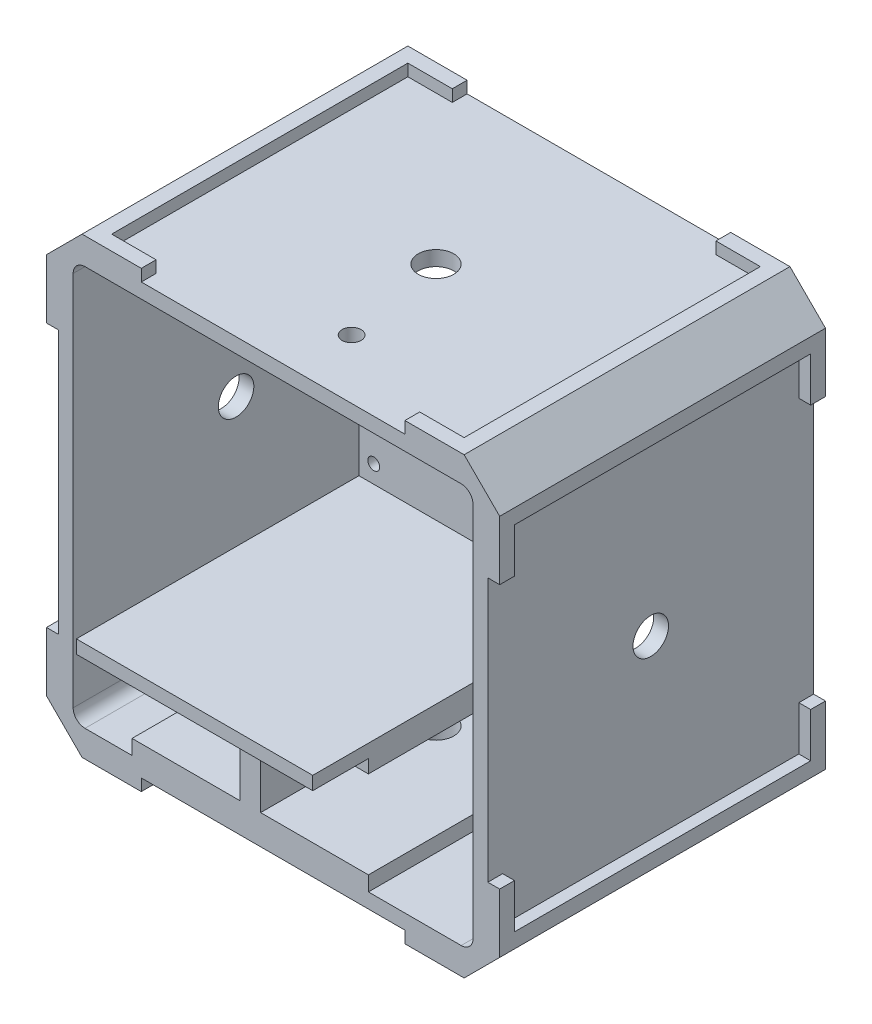
SolidWorks part; units mm, degrees
ref_plane "Front Plane" through (0, 0, 0) normal (0, 0, 1) x (1, 0, 0)
ref_plane "Top Plane" through (0, 0, 0) normal (0, 1, 0) x (1, 0, 0)
ref_plane "Right Plane" through (0, 0, 0) normal (1, 0, 0) x (0, 0, -1)
sketch "Sketch1" plane through (0, 0, 0) normal (0, 0, 1) x (1, 0, 0)
  line L0 (-33.75, -33.75) -> (33.75, -33.75) construction
  line L1 (-31.75, 33.75) -> (31.75, 33.75)
  line L2 (-33.75, 31.75) -> (-33.75, -31.75)
  line L3 (-31.75, -33.75) -> (31.75, -33.75)
  line L4 (33.75, 31.75) -> (33.75, -31.75)
  line L5 (-36.25, 32.25) -> (-36.25, -32.25)
  line L6 (33.75, 33.75) -> (33.75, -33.75) construction
  line L7 (-32.25, -36.25) -> (32.25, -36.25)
  line L8 (36.25, 32.25) -> (36.25, -32.25)
  line L9 (-32.25, 36.25) -> (32.25, 36.25)
  line L10 (-36.25, 36.25) -> (-36.25, -36.25) construction
  line L11 (-36.25, 36.25) -> (36.25, 36.25) construction
  line L12 (-33.75, 33.75) -> (33.75, 33.75) construction
  line L13 (-33.75, 33.75) -> (-33.75, -33.75) construction
  line L14 (-36.25, -36.25) -> (36.25, -36.25) construction
  line L15 (36.25, 36.25) -> (36.25, -36.25) construction
  line L16 (55, 0) -> (-55, 0) construction
  line L17 (0, -55) -> (0, 55) construction
  arc A0 (-36.25, 32.25) -> (-32.25, 36.25) centre (-32.25, 32.25) cw
  arc A1 (-31.75, 33.75) -> (-33.75, 31.75) centre (-31.75, 31.75) ccw
  arc A2 (-33.75, -31.75) -> (-31.75, -33.75) centre (-31.75, -31.75) ccw
  arc A3 (31.75, -33.75) -> (33.75, -31.75) centre (31.75, -31.75) ccw
  arc A4 (31.75, 33.75) -> (33.75, 31.75) centre (31.75, 31.75) cw
  arc A5 (-36.25, -32.25) -> (-32.25, -36.25) centre (-32.25, -32.25) ccw
  arc A6 (32.25, -36.25) -> (36.25, -32.25) centre (32.25, -32.25) ccw
  arc A7 (36.25, 32.25) -> (32.25, 36.25) centre (32.25, 32.25) ccw
  point P36 (-33.75, 0)
  point P39 (0, 33.75)
  dimension "D3" = 4
  dimension "D4" = 2
  dimension "D5" = 2
  dimension "D6" = 4
  dimension "D1" = 67.5
  dimension "D2" = 2.5
extrude "Boss-Extrude1" add sketch "Sketch1" along normal blind 55
sketch "Sketch2" plane through (0, 0, 0) normal (0, 0, 1) x (1, 0, 0)
  line L1 (-33.75, 33.75) -> (33.75, 33.75)
  line L2 (-33.75, 33.75) -> (-33.75, -33.75)
  line L3 (-33.75, -33.75) -> (33.75, -33.75)
  line L4 (33.75, 33.75) -> (33.75, -33.75)
extrude "Boss-Extrude2" add sketch "Sketch2" along normal blind 2.5
sketch "Sketch3" plane through (0, 0, 2.5) normal (0, 0, 1) x (1, 0, 0)
  line L0 (-4.38, 17.29) -> (-18.88, 12.29) construction
  line L1 (-19.88, 11.29) -> (-3.38, 11.29)
  line L2 (-18.88, 12.29) -> (-4.38, 12.29) construction
  line L3 (-18.88, 12.29) -> (-18.88, 17.29) construction
  line L4 (-18.88, 17.29) -> (-4.38, 17.29) construction
  line L5 (-4.38, 12.29) -> (-4.38, 17.29) construction
  line L6 (-3.38, 11.29) -> (-3.38, 18.29)
  line L7 (-19.88, 18.29) -> (-3.38, 18.29)
  line L8 (-19.88, 11.29) -> (-19.88, 18.29)
  line L9 (-36.25, 32.25) -> (-36.25, -32.25) construction
  line L10 (-3, -7) -> (3, -7) construction
  line L11 (-3, -7) -> (-3, 7) construction
  line L12 (-3, 7) -> (3, 7) construction
  line L13 (3, -7) -> (3, 7) construction
  line L14 (-3, -7) -> (3, 7) construction
  line L15 (-3, 7) -> (3, -7) construction
  line L16 (32.25, 36.25) -> (-32.25, 36.25) construction
  line L17 (-4, -8) -> (-4, 8)
  line L18 (-4, 8) -> (4, 8)
  line L19 (4, -8) -> (4, 8)
  line L20 (-4, -8) -> (4, -8)
  line L21 (-18.88, 17.29) -> (-4.38, 12.29) construction
  point P0 (0, 0)
  dimension "D2" = 6
  dimension "D3" = 14
  dimension "D5" = 14.5
  dimension "D6" = 5
  dimension "D7" = 16.37
  dimension "D8" = 23.96
  dimension "D1" = 1
  dimension "D4" = 1
extrude "Cut-Extrude1" cut sketch "Sketch3" against normal up to next
fillet "Fillet1" radius 1 8 edges at (-19.88, 11.29, 1.25) (-19.88, 18.29, 1.25) (-3.38, 18.29, 1.25) (-3.38, 11.29, 1.25) (4, -8, 1.25) (-4, -8, 1.25) (-4, 8, 1.25) (4, 8, 1.25)
sketch "Sketch4" plane through (0, 0, 0) normal (0, 0, -1) x (-1, 0, 0)
  line L0 (-32.25, 36.25) -> (32.25, 36.25) construction
  line L1 (-36.25, -32.25) -> (-36.25, 32.25) construction
  circle A0 centre (-28.75, 28.75) radius 1.5
  dimension "D3" = 3
  dimension "D1" = 7.5
  dimension "D2" = 7.5
extrude "Cut-Extrude2" cut sketch "Sketch4" against normal up to next
mirror "Mirror1" about plane through (0, 0, 0) normal (1, 0, 0) of "Cut-Extrude2"
mirror "Mirror2" about plane through (0, 0, 0) normal (0, 1, 0) of "Mirror1"
sketch "Sketch5" plane through (0, 0, 0) normal (1, 0, 0) x (0, 0, -1)
  line L2 (-16.7, 12) -> (-16.7, -12)
  line L3 (-16.7, -12) -> (-62.4, -12)
  line L6 (-14.7, -14) -> (-64.4, -14)
  line L7 (-14.7, 12) -> (-14.7, -14)
  line L9 (-62.4, -12) -> (-64.4, -12)
  line L10 (-64.4, -12) -> (-64.4, -14)
  line L11 (-62.4, 12) -> (-62.4, -12) construction
  line L12 (-64.4, 14) -> (-64.4, -14) construction
  line L15 (-16.7, 12) -> (-14.7, 12)
  line L16 (-14.7, 14) -> (-14.7, -14) construction
  line L17 (-14.7, 14) -> (-64.4, 14) construction
  line L18 (-16.7, 12) -> (-62.4, 12) construction
  dimension "D1" = 24
  dimension "D2" = 49.7
  dimension "D3" = 2
extrude "Boss-Extrude3" add sketch "Sketch5" along normal blind 16.09 and the other way blind 23.81 separate body
sketch "Sketch6" plane through (0, 0, 64.4) normal (0, 0, 1) x (1, 0, 0)
  line L0 (-23.81, -14) -> (16.09, -14) construction
  line L1 (-23.81, -14) -> (16.09, -14)
  line L2 (-23.81, -14) -> (-23.81, -16.5)
  line L3 (-23.81, -16.5) -> (-5.61, -16.5)
  line L4 (16.09, -14) -> (16.09, -16.5)
  line L5 (-31.75, -33.75) -> (31.75, -33.75) construction
  line L6 (-23.81, -33.75) -> (16.09, -33.75)
  line L7 (-23.81, -33.75) -> (-23.81, -31.25)
  line L8 (-23.81, -31.25) -> (-5.61, -31.25)
  line L9 (16.09, -33.75) -> (16.09, -31.25)
  line L10 (-2.11, -16.5) -> (16.09, -16.5)
  line L12 (-5.61, -16.5) -> (-5.61, -31.25)
  line L14 (-2.11, -16.5) -> (-2.11, -31.25)
  line L15 (-2.11, -31.25) -> (16.09, -31.25)
  line L16 (-23.81, -12) -> (-23.81, -14) construction
  dimension "D1" = 2.5
  dimension "D2" = 2.5
  dimension "D3" = 39.9
  dimension "D4" = 39.9
  dimension "D5" = 3.5
  dimension "D6" = 18.2
  dimension "D7" = 18.2
extrude "Boss-Extrude4" add sketch "Sketch6" against normal blind 47
sketch "Sketch7" plane through (0, 0, 64.4) normal (0, 0, 1) x (1, 0, 0)
  line L0 (-23.81, -12) -> (-23.81, -16.5) construction
  line L1 (-23.81, -14.25) -> (16.09, -14.25)
  line L2 (-23.81, -14.25) -> (-23.81, -33.75)
  line L3 (-23.81, -33.75) -> (16.09, -33.75)
  line L4 (16.09, -14.25) -> (16.09, -33.75)
  line L5 (16.09, -33.75) -> (31.75, -33.75) construction
  line L6 (16.09, -33.75) -> (16.09, -31.25) construction
extrude "Cut-Extrude3" cut sketch "Sketch7" against normal blind 9.4
sketch "Sketch9" [suppressed] plane through (-15.56, 0, 0) normal (-1, 0, 0) x (0, 0, 1)
  circle A0 centre (22.3967, 9) radius 1
  circle A1 centre (22.3967, 9) radius 2
  dimension "D1" = 2
  dimension "D2" = 1
extrude "Boss-Extrude6" [suppressed] add sketch "Sketch9" along normal blind 1.5
ref_plane "Plane1" through (-9.11, 0, 0) normal (-1, 0, 0) x (0, 0, 1)
sketch "Sketch10" [suppressed] plane through (-36.25, 0, 0) normal (-1, 0, 0) x (0, 0, 1)
  circle A0 centre (22.3967, 9) radius 1.5
  circle A1 centre (22.3967, -9) radius 1.5
  dimension "D1" = 3
  dimension "D2" = 3
extrude "Cut-Extrude4" [suppressed] cut sketch "Sketch10" against normal through all
sketch "Sketch12" plane through (0, 36.25, 0) normal (0, 1, 0) x (1, 0, 0)
  line L0 (-32.25, -55) -> (-32.25, 0) construction
  line L1 (32.25, -55) -> (29.75, -55)
  line L2 (32.25, -55) -> (32.25, -45)
  line L3 (32.25, -45) -> (29.75, -45)
  line L4 (29.75, -52.5) -> (29.75, -45)
  line L5 (32.25, -55) -> (22.25, -55)
  line L6 (32.25, -55) -> (32.25, -52.5)
  line L7 (29.75, -52.5) -> (22.25, -52.5)
  line L8 (22.25, -55) -> (22.25, -52.5)
  line L10 (-32.25, 0) -> (-32.25, -10)
  line L11 (-32.25, -10) -> (-29.75, -10)
  line L12 (-29.75, -2.5) -> (-29.75, -10)
  line L13 (-32.25, 0) -> (-22.25, 0)
  line L15 (-29.75, -2.5) -> (-22.25, -2.5)
  line L16 (-22.25, 0) -> (-22.25, -2.5)
  line M6 (-32.25, -55) -> (32.25, -55)
  line M7 (32.25, -55) -> (32.25, 0)
  dimension "D1" = 2.5
  dimension "D2" = 10
  dimension "D3" = 2.5
  dimension "D4" = 10
  dimension "D5" = 2.5
extrude "Boss-Extrude7" add sketch "Sketch12" along normal blind 2 contours L8 L2 L3 L4 L7 M6 M7 | L10 L11 L12 L15 L16 L13 region at (31, 36.25, 54.8586)
sketch "Sketch13" plane through (0, 0, 0) normal (0, 0, -1) x (-1, 0, 0)
  line L3 (-33.75, 21.25) -> (-25.25, 21.25)
  line L4 (-21.25, 33.75) -> (-21.25, 25.25)
  line L6 (0, 35.42) -> (0, -35.42) construction
  line L8 (21.25, 33.75) -> (21.25, 25.25)
  line L9 (33.75, 21.25) -> (25.25, 21.25)
  line L12 (35.42, 0) -> (-35.42, 0) construction
  line L17 (33.75, -21.25) -> (25.25, -21.25)
  line L18 (21.25, -33.75) -> (21.25, -25.25)
  line L19 (-21.25, -33.75) -> (-21.25, -25.25)
  line L20 (-33.75, -21.25) -> (-25.25, -21.25)
  line L27 (-33.75, 21.25) -> (-33.75, -21.25)
  line L29 (33.75, 21.25) -> (33.75, -21.25)
  line L34 (-21.25, 33.75) -> (21.25, 33.75)
  line L36 (-21.25, -33.75) -> (21.25, -33.75)
  arc A2 (-25.25, 21.25) -> (-21.25, 25.25) centre (-25.25, 25.25) ccw
  arc A4 (25.25, 21.25) -> (21.25, 25.25) centre (25.25, 25.25) cw
  arc A7 (25.25, -21.25) -> (21.25, -25.25) centre (25.25, -25.25) ccw
  arc A8 (-25.25, -21.25) -> (-21.25, -25.25) centre (-25.25, -25.25) cw
  dimension "D3" = 4
extrude "Cut-Extrude6" cut sketch "Sketch13" against normal up to next and the other way through all
sketch "Sketch15" plane through (0, 36.25, 0) normal (0, 1, 0) x (1, 0, 0)
  line L0 (22.25, -55) -> (-32.25, -55) construction
  line L1 (33.75, -55) -> (33.75, -2.5) construction
  circle A0 centre (3.25, -45) radius 1.6
  dimension "D1" = 3.2
  dimension "D2" = 10
  dimension "D3" = 30.5
extrude "Cut-Extrude8" cut sketch "Sketch15" against normal up to surface (2.5 mm away) and the other way through all up to face at (0, 33.75, 15)
sketch "Sketch16" plane through (-33.75, 0, 0) normal (1, 0, 0) x (0, 0, -1)
  line L2 (-16, 32.15) -> (-16, 29.65)
  line L7 (-16, 29.65) -> (-8.5, 29.65)
  line L9 (-16, 32.15) -> (-8.5, 32.15)
  line L10 (-8.5, 29.65) -> (-8.5, 32.15)
  line L12 (0, -32.25) -> (0, 32.25) construction
  dimension "D1" = 7.5
  dimension "D3" = 16
extrude "Boss-Extrude8" add sketch "Sketch16" along normal blind 7
sketch "Sketch17" plane through (0, 0, 14.7) normal (0, 0, -1) x (-1, 0, 0)
  line L0 (-16.09, -14) -> (-16.09, 12) construction
  line L2 (23.81, -14) -> (23.81, 12) construction
  line L3 (23.81, 12) -> (-16.09, 12) construction
  circle A0 centre (-13.59, 9) radius 1
  circle A1 centre (-13.59, -9) radius 1
  circle A2 centre (21.31, -9) radius 1
  dimension "D1" = 2
  dimension "D2" = 2.5
  dimension "D3" = 3
  dimension "D4" = 2.5
  dimension "D6" = 18
extrude "Cut-Extrude9" cut sketch "Sketch17" against normal up to next
sketch "Sketch19" plane through (0, 36.25, 0) normal (0, 1, 0) x (1, 0, 0)
  line L0 (32.25, -55) -> (-32.25, 0) construction
  line L1 (-32.25, 0) -> (-22.25, 0) construction
  line L2 (32.25, 0) -> (-32.25, -55) construction
  line L3 (32.25, -45) -> (32.25, 0) construction
  line L4 (32.25, 0) -> (-22.25, 0) construction
  line L5 (-32.25, 0) -> (-32.25, -10) construction
  line L6 (-32.25, 0) -> (-32.25, -10) construction
  circle A0 centre (0, -27.5) radius 3
  dimension "D1" = 6
extrude "Cut-Extrude10" cut sketch "Sketch19" against normal blind 2.5
sketch "Sketch20" plane through (36.25, 0, -36.25) normal (-1, 0, 0) x (0, 0, 1)
  line L0 (36.25, -32.25) -> (36.25, 32.25) construction
  line L1 (36.25, -32.25) -> (36.25, -22.25)
  line L2 (36.25, -32.25) -> (46.25, -32.25)
  line L3 (46.25, -32.25) -> (46.25, -29.75)
  line L4 (38.75, -29.75) -> (46.25, -29.75)
  line L5 (36.25, -32.25) -> (36.25, -22.25)
  line L7 (38.75, -29.75) -> (38.75, -22.25)
  line L8 (36.25, -22.25) -> (38.75, -22.25)
  line L10 (91.25, 32.25) -> (81.25, 32.25)
  line L11 (81.25, 32.25) -> (81.25, 29.75)
  line L12 (88.75, 29.75) -> (81.25, 29.75)
  line L13 (91.25, 32.25) -> (91.25, 22.25)
  line L15 (88.75, 29.75) -> (88.75, 22.25)
  line L16 (91.25, 22.25) -> (88.75, 22.25)
  line M25 (36.25, -32.25) -> (36.25, 32.25)
  line M26 (36.25, 32.25) -> (91.25, 32.25)
  line M27 (91.25, 32.25) -> (91.25, -32.25)
  line M28 (91.25, -32.25) -> (36.25, -32.25)
  dimension "D1" = 2.5
  dimension "D2" = 10
  dimension "D3" = 2.5
  dimension "D4" = 10
  dimension "D5" = 2.5
  dimension "D6" = 55
  dimension "D7" = 64.5
  dimension "D8" = 10
  dimension "D9" = 7.5
  dimension "D10" = 7.5
extrude "Boss-Extrude9" add sketch "Sketch20" against normal blind 2 contours L16 L15 L12 L11 M27 M26 | L8 L7 L4 L3 M25 M28 region at (36.25, -27.25, 0.1414) region at (36.25, 32.1086, 50)
ref_axis "Axis1" through (0, 0, 67.62) along (0, 0, -1)
pattern_circular "CirPattern1" count 4 every 90 about axis through (0, 0, 67.62) along (0, 0, -1) of "Boss-Extrude7", "Cut-Extrude10"
pattern_circular "CirPattern2" count 4 every 90 about axis through (0, 0, 67.62) along (0, 0, -1) of "Boss-Extrude9"
sketch "Sketch21" plane through (0, -33.75, 0) normal (0, -1, 0) x (1, 0, 0)
  line L0 (-2.11, 25.3674) -> (-2.11, 29.6326)
  arc A0 (-2.11, 25.3674) -> (-2.11, 29.6326) centre (0, 27.5) ccw
extrude "Cut-Extrude11" cut sketch "Sketch21" against normal blind 2.5
sketch "Sketch22" plane through (0, 0, 55) normal (0, 0, 1) x (1, 0, 0)
  line L0 (-38.25, 32.25) -> (-32.25, 38.25)
  line L1 (-32.25, 38.25) -> (-29.75, 38.25)
  line L8 (-29.75, 38.25) -> (-29.75, 33.75)
  line L13 (-38.25, 29.75) -> (-33.75, 29.75)
  line L20 (-38.25, 29.75) -> (-38.25, 32.25)
  line L24 (-32.25, 38.25) -> (-22.25, 38.25) construction
  line L26 (-33.75, 31.75) -> (-33.75, -31.75) construction
  line L27 (-38.25, 22.25) -> (-38.25, 32.25) construction
  line L28 (0, -35.42) -> (0, 35.42) construction
  line L29 (33.75, 33.75) -> (33.75, 29.75)
  line L30 (33.75, 33.75) -> (29.75, 33.75)
  line L31 (38.25, 29.75) -> (38.25, 32.25)
  line L32 (38.25, 29.75) -> (33.75, 29.75)
  line L33 (-33.75, 33.75) -> (-29.75, 33.75)
  line L34 (-33.75, 33.75) -> (-33.75, 29.75)
  line L37 (29.75, 38.25) -> (29.75, 33.75)
  line L38 (32.25, 38.25) -> (29.75, 38.25)
  line L39 (38.25, 32.25) -> (32.25, 38.25)
  line L40 (35.42, 0) -> (-35.42, 0) construction
  line L41 (38.25, -32.25) -> (32.25, -38.25)
  line L42 (32.25, -38.25) -> (29.75, -38.25)
  line L43 (29.75, -38.25) -> (29.75, -33.75)
  line L44 (-33.75, -33.75) -> (-33.75, -29.75)
  line L45 (-33.75, -33.75) -> (-29.75, -33.75)
  line L46 (38.25, -29.75) -> (33.75, -29.75)
  line L47 (38.25, -29.75) -> (38.25, -32.25)
  line L48 (33.75, -33.75) -> (29.75, -33.75)
  line L49 (33.75, -33.75) -> (33.75, -29.75)
  line L50 (-38.25, -29.75) -> (-38.25, -32.25)
  line L51 (-38.25, -29.75) -> (-33.75, -29.75)
  line L52 (-29.75, -38.25) -> (-29.75, -33.75)
  line L53 (-32.25, -38.25) -> (-29.75, -38.25)
  line L54 (-38.25, -32.25) -> (-32.25, -38.25)
  dimension "D1" = 2.5
  dimension "D2" = 2.5
extrude "Boss-Extrude12" add sketch "Sketch22" against normal through all
sketch "Sketch23" plane through (0, 0, 14.7) normal (0, 0, -1) x (-1, 0, 0)
  line L0 (23.81, 12) -> (-16.09, 12) construction
  line L1 (18.31, 12) -> (23.81, 12)
  line L2 (18.31, 12) -> (18.31, -4)
  line L3 (18.31, -4) -> (23.81, -4)
  line L4 (23.81, 12) -> (23.81, -4)
  line L5 (23.81, -14) -> (23.81, 12) construction
  circle A0 centre (21.31, -9) radius 1 construction
  dimension "D1" = 5
  dimension "D2" = 5.5
extrude "Cut-Extrude12" cut sketch "Sketch23" against normal up to next
sketch "Sketch24" plane through (16.09, 0, 0) normal (1, 0, 0) x (0, 0, -1)
  line L0 (-14.7, -14) -> (-14.7, 12) construction
  line L1 (-17.4, -16.5) -> (-17.4, -13.792)
  line L2 (-17.4, -13.792) -> (-14.7, -14)
  arc A0 (-14.7, -14) -> (-17.4, -16.5) centre (-17.4, -13.792) cw
extrude "Boss-Extrude13" add sketch "Sketch24" against normal up to surface (39.9 mm away) up to face at (-23.81, -12.15, 33.64)
fillet "Fillet2" radius 1.5 1 edges at (16.09, 12, 15.7)
chamfer "Chamfer1" distance 0.5 angle 45 2 edges at (-26.75, 32.15, 12.25) (-30.2298, 32.15, 16)
